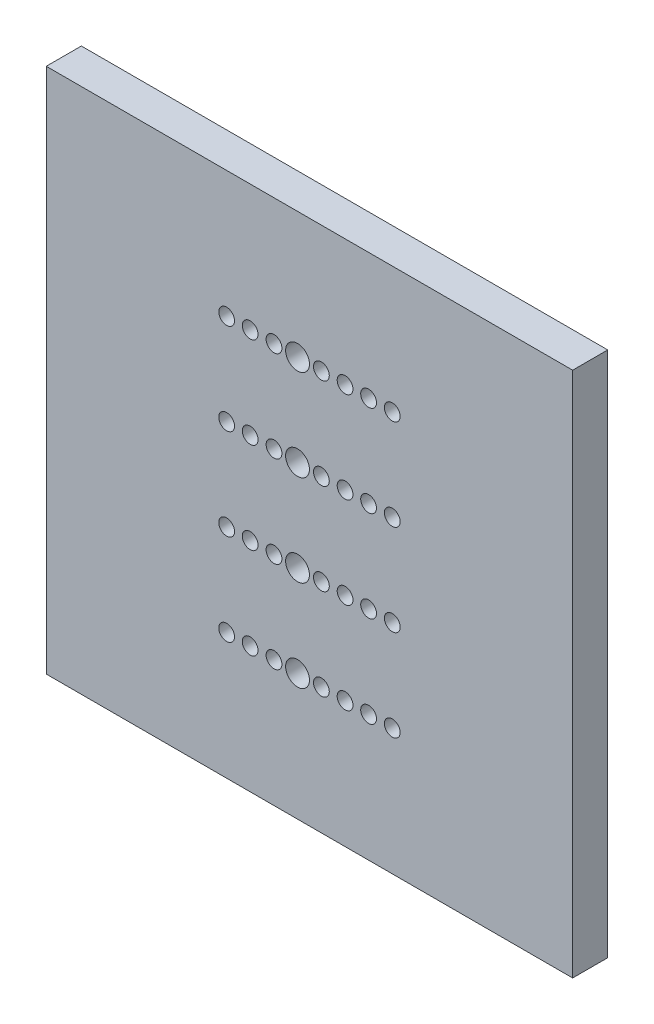
SolidWorks part; units mm, degrees
ref_plane "Plan de face" through (0, 0, 0) normal (0, 0, 1) x (1, 0, 0)
ref_plane "Plan de dessus" through (0, 0, 0) normal (0, 1, 0) x (1, 0, 0)
ref_plane "Plan de droite" through (0, 0, 0) normal (1, 0, 0) x (0, 0, -1)
sketch "Esquisse2" plane through (0, 0, 0) normal (0, 0, 1) x (1, 0, 0)
  line L1 (-15, -15) -> (15, -15)
  line L2 (-15, -15) -> (-15, 15)
  line L3 (-15, 15) -> (15, 15)
  line L4 (15, -15) -> (15, 15)
  line L5 (-15, -15) -> (15, 15) construction
  line L6 (-15, 15) -> (15, -15) construction
  point P0 (0, 0)
extrude "Boss.-Extru.1" add sketch "Esquisse2" along normal blind 2
sketch "Esquisse3" plane through (0, 0, 2) normal (0, 0, 1) x (1, 0, 0)
  circle A0 centre (-4.72, -7.8) radius 0.45
  circle A1 centre (-4.72, -2.6) radius 0.45
  circle A2 centre (-4.72, 2.6) radius 0.45
  circle A3 centre (-4.72, 7.8) radius 0.45
  circle A4 centre (-3.38, -7.8) radius 0.45
  circle A5 centre (-3.38, -2.6) radius 0.45
  circle A6 centre (-3.38, 2.6) radius 0.45
  circle A7 centre (-3.38, 7.8) radius 0.45
  circle A8 centre (-2.02, -7.8) radius 0.45
  circle A9 centre (-2.02, -2.6) radius 0.45
  circle A10 centre (-2.02, 2.6) radius 0.45
  circle A11 centre (-2.02, 7.8) radius 0.45
  circle A12 centre (-0.68, -7.8) radius 0.68
  circle A13 centre (-0.68, -2.6) radius 0.68
  circle A14 centre (-0.68, 2.6) radius 0.68
  circle A15 centre (-0.68, 7.8) radius 0.68
  circle A16 centre (0.68, -7.8) radius 0.45
  circle A17 centre (0.68, -2.6) radius 0.45
  circle A18 centre (0.68, 2.6) radius 0.45
  circle A19 centre (0.68, 7.8) radius 0.45
  circle A20 centre (2.03, -7.8) radius 0.45
  circle A21 centre (2.03, -2.6) radius 0.45
  circle A22 centre (2.03, 2.6) radius 0.45
  circle A23 centre (2.03, 7.8) radius 0.45
  circle A24 centre (3.37, -7.8) radius 0.45
  circle A25 centre (3.37, -2.6) radius 0.45
  circle A26 centre (3.37, 2.6) radius 0.45
  circle A27 centre (3.37, 7.8) radius 0.45
  circle A28 centre (4.72, -7.8) radius 0.45
  circle A29 centre (4.72, -2.6) radius 0.45
  circle A30 centre (4.72, 2.6) radius 0.45
  circle A31 centre (4.72, 7.8) radius 0.45
extrude "Enlèv. mat.-Extru.1" cut sketch "Esquisse3" against normal blind 10
